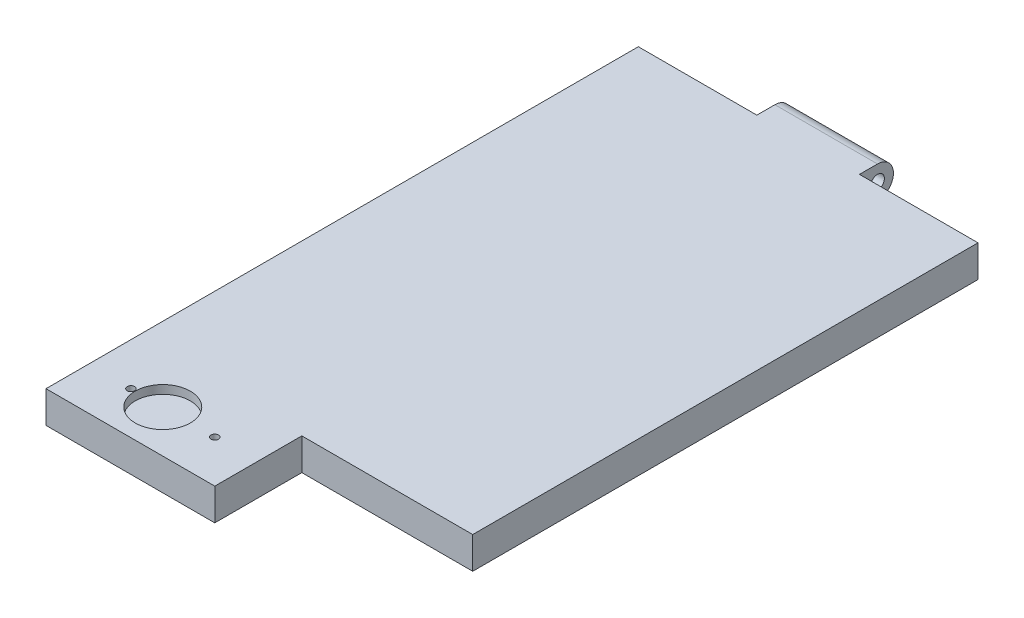
SolidWorks part; units mm, degrees
note: The reader was unsure of these and kept them because the rebuilt part matched: shared geometry of "草图2<3>".
ref_plane "前视基准面" through (0, 0, 0) normal (0, 0, 1) x (1, 0, 0)
ref_plane "上视基准面" through (0, 0, 0) normal (0, 1, 0) x (1, 0, 0)
ref_plane "右视基准面" through (0, 0, 0) normal (1, 0, 0) x (0, 0, -1)
other "Configuration Table"
sketch "草图1" plane through (0, 0, 0) normal (0, 1, 0) x (1, 0, 0)
  line L0 (16, -56) -> (16, 47.4774) construction
  line L1 (0, -56) -> (32, -56)
  line L2 (0, -56) -> (0, 0)
  line L3 (0, 0) -> (32, 0)
  line L4 (32, -56) -> (32, 0)
  line L6 (15.9, -56) -> (32, -56)
  line L7 (15.9, -56) -> (15.9, -47.8)
  line L8 (15.9, -47.8) -> (32, -47.8)
  line L9 (32, -56) -> (32, -47.8)
  point P0 (0, 0)
  dimension "D3" = 0.1
  dimension "D4" = 8.2
  dimension "D1" = 32
  dimension "D2" = 56
extrude "凸台-拉伸1" add sketch "草图1" along normal blind 3 contours L0 L6 L4 L8 | L1 L0 L8 L7
sketch "草图2" plane through (0, 0, 0) normal (0, 0, -1) x (-1, 0, 0)
  line L0 (0, 0) -> (-32, 0) construction
  line L1 (-10.6667, 0) -> (-21.3333, 0)
  line L2 (-10.6667, 0) -> (-10.6667, 3)
  line L3 (-10.6667, 3) -> (-21.3333, 3)
  line L4 (-21.3333, 0) -> (-21.3333, 3)
  line L5 (0, 3) -> (-32, 3) construction
  line L6 (0, 1.5) -> (-10.6667, 1.5) construction
  line L7 (0, 3) -> (0, 0) construction
  line L8 (-10.6667, 1.5) -> (-21.3333, 1.5) construction
  line L9 (-21.3333, 1.5) -> (-32, 1.5) construction
  line L10 (-32, 3) -> (-32, 0) construction
  line L12 (-11.1667, 3) -> (-20.8333, 3)
  line L13 (-11.1667, 3) -> (-11.1667, 0)
  line L14 (-11.1667, 0) -> (-20.8333, 0)
  line L15 (-20.8333, 3) -> (-20.8333, 0)
  line M12 (-32, 0) -> (0, 0)
  line M13 (0, 0) -> (0, 3)
  line M14 (0, 3) -> (-32, 3)
  line M15 (-32, 3) -> (-32, 0)
  dimension "D1" = 0.5
  dimension "D2" = 0.5
extrude "凸台-拉伸2" add sketch "草图2" along normal blind 3 contours L3 L15 L1 L13
fillet "圆角1" radius 1.5 2 edges at (16, 3, -3) (16, 0, -3)
sketch "草图3" plane through (11.1667, 0, 0) normal (-1, 0, 0) x (0, 0, 1)
  circle A0 centre (-1.5, 1.5) radius 0.65
  arc A1 (-3, 1.5) -> (-1.5, 0) centre (-1.5, 1.5) ccw construction
  dimension "D1" = 1.3
extrude "切除-拉伸1" cut sketch "草图3" against normal through all
extrude "切除-拉伸2" cut sketch "草图2<3>" against normal blind 0.2 contours L2 M12 M13 M14 | L13 L1 L2 M14 | L15 L4 M14 M12 | L4 M12 M14 M15
sketch "草图2<3>" plane through (0, 0, 0) normal (0, 0, -1) x (-1, 0, 0) same geometry as "草图2"
sketch "草图4" plane through (0, 3, 0) normal (0, 1, 0) x (1, 0, 0)
  line L0 (0, -56) -> (0, -0.2) construction
  line L1 (0, -56) -> (15.9, -56) construction
  circle A1 centre (7, -52) radius 2.6
  dimension "D2" = 5.2
  dimension "D1" = 7
  dimension "D3" = 4
extrude "切除-拉伸3" cut sketch "草图4" against normal blind 0.8
sketch "草图5" plane through (0, 0, 0) normal (0, -1, 0) x (1, 0, 0)
  line L0 (0, 56) -> (15.9, 56) construction
  line L1 (15.9, 56) -> (15.9, 47.8) construction
  line L2 (0, 56) -> (0, 0.2) construction
  circle A0 centre (11.9, 52) radius 0.35
  circle A1 centre (4, 52) radius 0.35
  dimension "D2" = 0.7
  dimension "D1" = 4
  dimension "D3" = 4
  dimension "D4" = 4
extrude "切除-拉伸4" cut sketch "草图5" against normal through all
